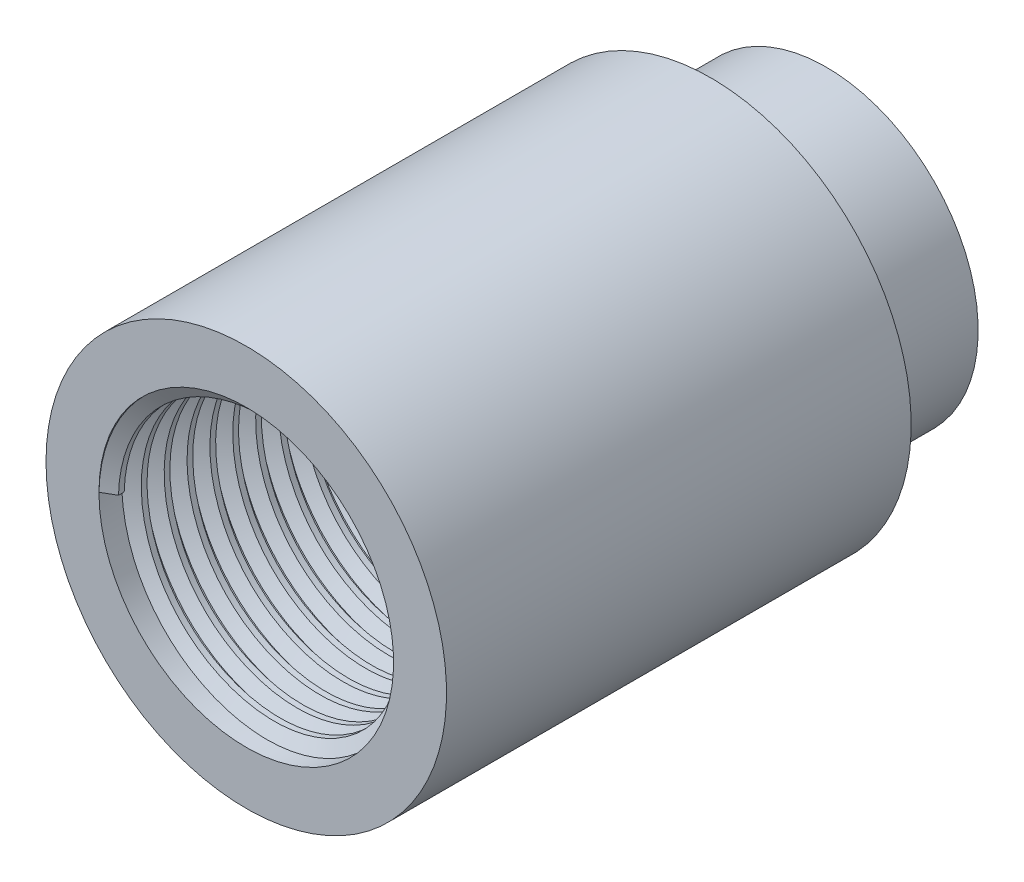
SolidWorks part; units mm, degrees
ref_plane "Front Plane" through (0, 0, 0) normal (0, 0, 1) x (1, 0, 0)
ref_plane "Top Plane" through (0, 0, 0) normal (0, 1, 0) x (1, 0, 0)
ref_plane "Right Plane" through (0, 0, 0) normal (1, 0, 0) x (0, 0, -1)
sketch "Sketch1" plane through (0, 0, 0) normal (0, 0, 1) x (1, 0, 0)
  circle A0 centre (0, 0) radius 2.78
  dimension "D1" = 5.56
extrude "Boss-Extrude1" add sketch "Sketch1" along normal blind 6.45 contours A0
sketch "Sketch2" plane through (0, 0, 0) normal (0, 0, -1) x (-1, 0, 0)
  circle A0 centre (0, 0) radius 2.11
  dimension "D1" = 4.22
extrude "Boss-Extrude2" add sketch "Sketch2" along normal blind 1.6 contours A0
sketch "Sketch4" plane through (0, 0, -1.6) normal (0, 0, -1) x (-1, 0, 0)
  circle A0 centre (0, 0) radius 2.045
  point P3 (0, 0)
  dimension "D1" = 4.09
extrude "Cut-Extrude2" cut sketch "Sketch4" against normal blind 10
sketch "Sketch5" plane through (0, 0, 0) normal (0, 0, -1) x (-1, 0, 0)
  circle A0 centre (0, 0) radius 2.045
thread "Thread2" pitch 0.3175 method extrude profile "Thread Profile4" start angle 0, offset 0, length 7.5, pitch 0.3175, diameter 4.09
ref_plane "Plane7" through (-2.045, 0, 6.45) normal (0, -1, 0) x (-1, 0, 0)
sketch "Thread Profile4" plane through (-2.045, 0, 6.45) normal (0, -1, 0) x (-1, 0, 0)
  line L0 (0, 0) -> (0, 0.3175) construction
  line L11 (0, 0) -> (0, 0.2778)
  line L12 (0, 0.2778) -> (-0.1719, 0.1786)
  line L13 (-0.1719, 0.1786) -> (-0.1719, 0.0992)
  line L15 (-0.1719, 0.0992) -> (0, 0)
  line L17 (-0.1719, 0.1389) -> (0, 0.1389) construction
  point P2 (0, 0)
  dimension "Pitch" = 0.3175
  dimension "Profile_Angle" = 60
  dimension "Profile_Land" = 0.0794
  dimension "Profile_Height" = 0.1719
